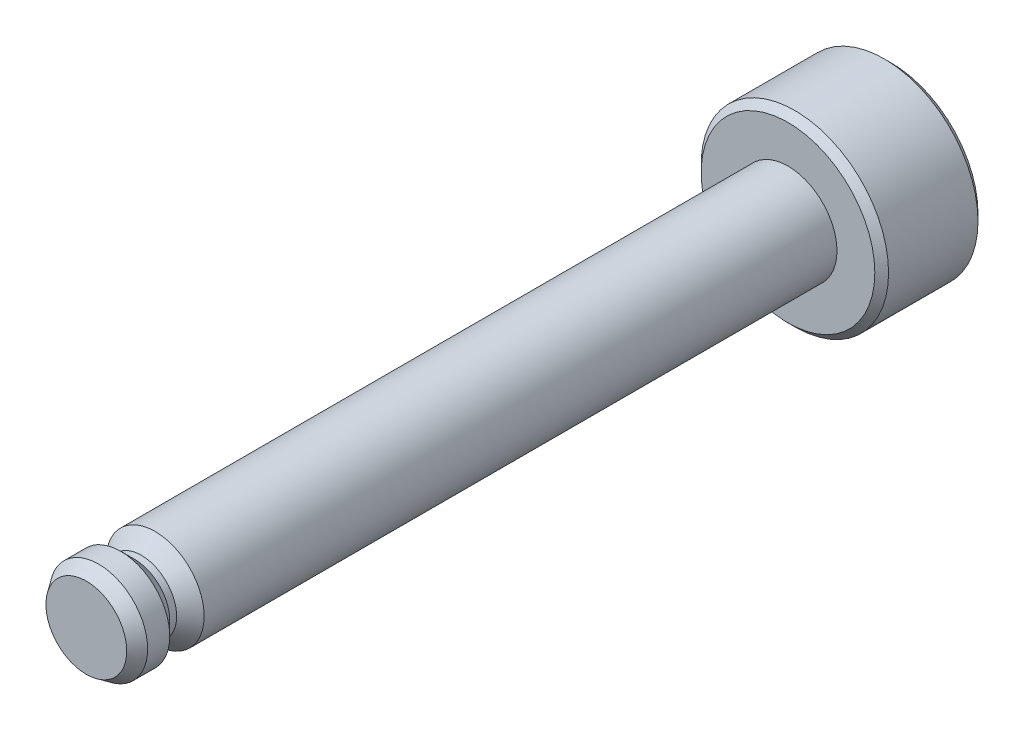
SolidWorks part; units mm, degrees
ref_plane "Front" through (0, 0, 0) normal (0, 0, 1) x (1, 0, 0)
ref_plane "Top" through (0, 0, 0) normal (0, 1, 0) x (1, 0, 0)
ref_plane "Right" through (0, 0, 0) normal (1, 0, 0) x (0, 0, -1)
sketch "Sketch2" plane through (0, 0, 0) normal (0, 0, 1) x (1, 0, 0)
  circle A0 centre (0, 0) radius 1.425
  dimension "D1" = 2.85
extrude "Shaft" add sketch "Sketch2" along normal blind 20.4
sketch "Sketch5" plane through (0, 0, 0) normal (0, 0, 1) x (1, 0, 0)
  circle A0 centre (0, 0) radius 2.725
  dimension "D1" = 5.45
extrude "Head" add sketch "Sketch5" against normal blind 3
sketch "Sketch4" plane through (0, 0, 0) normal (1, 0, 0) x (0, 0, -1)
  line L0 (0, 0) -> (-18.9, 0) construction
  line L1 (-18.9, 0) -> (-18.9, 4.3666) construction
  line L2 (-19.4, 1.425) -> (-18.4, 1.425)
  line L3 (0, 1.425) -> (-20.4, 1.425) construction
  line L6 (-18.4, 1.425) -> (-18.8, 1.025)
  line L7 (-18.8, 1.025) -> (-19, 1.025)
  line L8 (-19, 1.025) -> (-19.4, 1.425)
  line L10 (-18.9, 50) -> (-18.9, -50) construction
  dimension "D2" = 1
  dimension "D3" = 45
  dimension "D4" = 0.4
revolve "e-Clip Notch Short" cut sketch "Sketch4" angle 360 about L0
chamfer "Chamfer1" distance 0.25 angle 55 1 edges at (1.425, 0, 20.4) first distance on face at (1.425, 0, 20.4)
chamfer "Deburs" distance 0.2 angle 45 2 edges at (2.725, 0, 0) (2.725, 0, -3)
sketch "Sketch6" [suppressed] plane through (0, 0, 0) normal (1, 0, 0) x (0, 0, -1)
  line L0 (0, 0) -> (-28.9, 0) construction
  line L1 (-28.9, 0) -> (-28.9, 1.025) construction
  line L2 (0, 1.425) -> (-29.643, 1.425) construction
  line L3 (-29.4, 1.425) -> (-28.4, 1.425)
  line L4 (-28.4, 1.425) -> (-28.8, 1.025)
  line L5 (-28.8, 1.025) -> (-29, 1.025)
  line L6 (-29, 1.025) -> (-29.4, 1.425)
  line L7 (-28.9, 1.025) -> (-28.9, 1.425) construction
  line L8 (-19.4, 1.425) -> (-18.4, 1.425) construction
  line L9 (-19, 1.025) -> (-19.4, 1.425) construction
  line L10 (-28.9, 50) -> (-28.9, -50) construction
revolve "e-Clip Notch Long" [suppressed] cut sketch "Sketch6" angle 360 about L0
equation "\"D1@Sketch2\"=\"Plastic Hardware OD@Box Assy.Assembly\""
equation "\"D1@Sketch5\"=\"Hardware Head Countersink Diameter@Box Assy.Assembly\"-.3mm"
equation "\"D1@Head\"=\"Countersink Depth@Box Assy.Assembly\""
